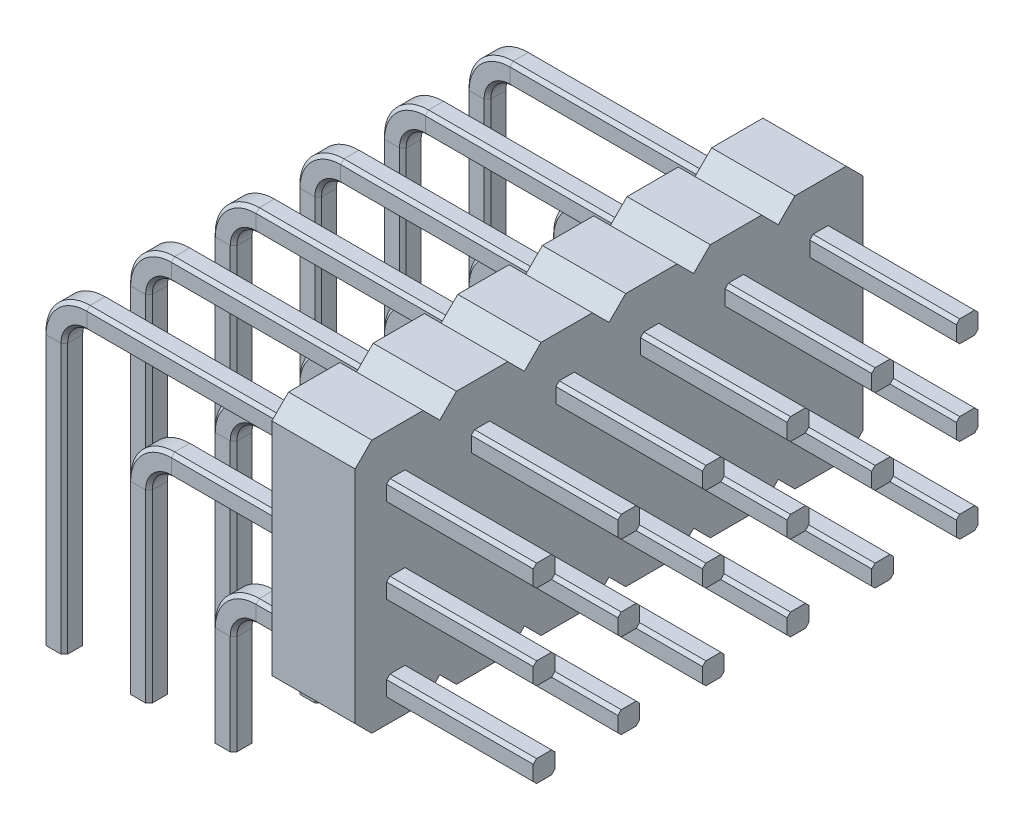
SolidWorks part; units mm, degrees
ref_plane "Front Plane" through (0, 0, 0) normal (0, 0, 1) x (1, 0, 0)
ref_plane "Top Plane" through (0, 0, 0) normal (0, 1, 0) x (1, 0, 0)
ref_plane "Right Plane" through (0, 0, 0) normal (1, 0, 0) x (0, 0, -1)
sketch "Sketch1" plane through (0, 0, 0) normal (0, 1, 0) x (1, 0, 0)
  line L0 (-0.225, 0.325) -> (-0.325, 0.225)
  line L1 (0.225, -0.325) -> (-0.225, -0.325)
  line L2 (0.325, -0.225) -> (0.325, 0.225)
  line L3 (0.225, 0.325) -> (-0.225, 0.325)
  line L4 (-0.325, -0.225) -> (-0.325, 0.225)
  line L5 (0.325, -0.325) -> (-0.325, 0.325) construction
  line L6 (0.325, 0.325) -> (-0.325, -0.325) construction
  line L7 (0.325, 0.225) -> (0.225, 0.325)
  line L8 (0.325, -0.225) -> (0.225, -0.325)
  line L9 (-0.225, -0.325) -> (-0.325, -0.225)
  line L10 (2.765, 0.325) -> (2.315, 0.325)
  line L11 (2.765, -0.325) -> (2.315, -0.325)
  line L12 (2.865, -0.225) -> (2.865, 0.225)
  line L13 (2.215, -0.225) -> (2.215, 0.225)
  line L14 (2.315, -0.325) -> (2.215, -0.225)
  line L15 (2.865, -0.225) -> (2.765, -0.325)
  line L16 (2.865, 0.225) -> (2.765, 0.325)
  line L17 (2.315, 0.325) -> (2.215, 0.225)
  line L18 (5.305, 0.325) -> (4.855, 0.325)
  line L19 (5.305, -0.325) -> (4.855, -0.325)
  line L20 (5.405, -0.225) -> (5.405, 0.225)
  line L21 (4.755, -0.225) -> (4.755, 0.225)
  line L22 (4.855, -0.325) -> (4.755, -0.225)
  line L23 (5.405, -0.225) -> (5.305, -0.325)
  line L24 (5.405, 0.225) -> (5.305, 0.325)
  line L25 (4.855, 0.325) -> (4.755, 0.225)
  line L26 (-3.1515, 0) -> (3.1515, 0) construction
  point P0 (0, 0)
  dimension "D1" = 0.65
  dimension "D2" = 3
sketch "Sketch2" plane through (0, 0, 0) normal (0, 0, 1) x (1, 0, 0)
  line L0 (0, 0) -> (0, 8.08)
  line L1 (1, 9.08) -> (14.4, 9.08)
  line L2 (2.54, 0) -> (2.54, 5.54)
  line L3 (2.765, 0) -> (2.315, 0) construction
  line L4 (3.54, 6.54) -> (14.4, 6.54)
  line L5 (5.08, 0) -> (5.08, 3)
  line L6 (5.305, 0) -> (4.855, 0) construction
  line L7 (6.08, 4) -> (14.4, 4)
  arc A0 (5.08, 3) -> (6.08, 4) centre (6.08, 3) cw
  arc A1 (2.54, 5.54) -> (3.54, 6.54) centre (3.54, 5.54) cw
  arc A2 (0, 8.08) -> (1, 9.08) centre (1, 8.08) cw
  point P17 (5.08, 4)
  point P20 (2.54, 6.54)
  point P23 (0, 9.08)
  dimension "D5" = 1
  dimension "D1" = 9.08
  dimension "D2" = 6.54
  dimension "D3" = 14.4
  dimension "D4" = 4
sweep "Sweep2" add profiles "Sketch1" path "Sketch2"
sweep "Sweep3" add profiles "Sketch1<9>" path "Sketch2<7>"
sketch "Sketch1<9>" plane through (0, 0, 0) normal (0, 1, 0) x (1, 0, 0) same geometry as "Sketch1"
sketch "Sketch2<7>" plane through (0, 0, 0) normal (0, 0, 1) x (1, 0, 0) same geometry as "Sketch2"
sweep "Sweep4" add profiles "Sketch1<10>" path "Sketch2<8>"
sketch "Sketch1<10>" plane through (0, 0, 0) normal (0, 1, 0) x (1, 0, 0) same geometry as "Sketch1"
sketch "Sketch2<8>" plane through (0, 0, 0) normal (0, 0, 1) x (1, 0, 0) same geometry as "Sketch2"
ref_plane "Plane4" through (7.5, 0, 0) normal (1, 0, 0) x (0, 0, -1)
sketch "Sketch5" plane through (7.5, 0, 0) normal (1, 0, 0) x (0, 0, -1)
  line L0 (0, 10.866) -> (0, 3) construction
  line L1 (0, 4) -> (0, 3) construction
  line L2 (0, 0) -> (0, 3) construction
  line L3 (-0.225, 9.405) -> (0.225, 9.405) construction
  line L4 (-0.77, 3.055) -> (0.77, 3.055)
  line L5 (-1.27, 3.555) -> (-1.27, 10.175)
  line L6 (-0.77, 10.675) -> (0.77, 10.675)
  line L7 (1.27, 3.555) -> (1.27, 10.175)
  line L8 (-1.27, 3.055) -> (1.27, 10.675) construction
  line L9 (-1.27, 10.675) -> (1.27, 3.055) construction
  line L10 (0.77, 10.675) -> (1.27, 10.175)
  line L11 (-1.27, 10.175) -> (-0.77, 10.675)
  line L12 (-1.27, 3.555) -> (-0.77, 3.055)
  line L13 (0.77, 3.055) -> (1.27, 3.555)
  point P6 (0, 6.865)
  dimension "D1" = 7.62
  dimension "D2" = 1.27
  dimension "D3" = 2.54
extrude "Boss-Extrude1" add sketch "Sketch5" along normal blind 2.5
pattern_linear "LPattern1" count 6 spacing 2.54 along (0, 0, 1) of bodies 105
combine bodies "Combine1" operation type add bodies to combine 105 106 107 108 109 110
